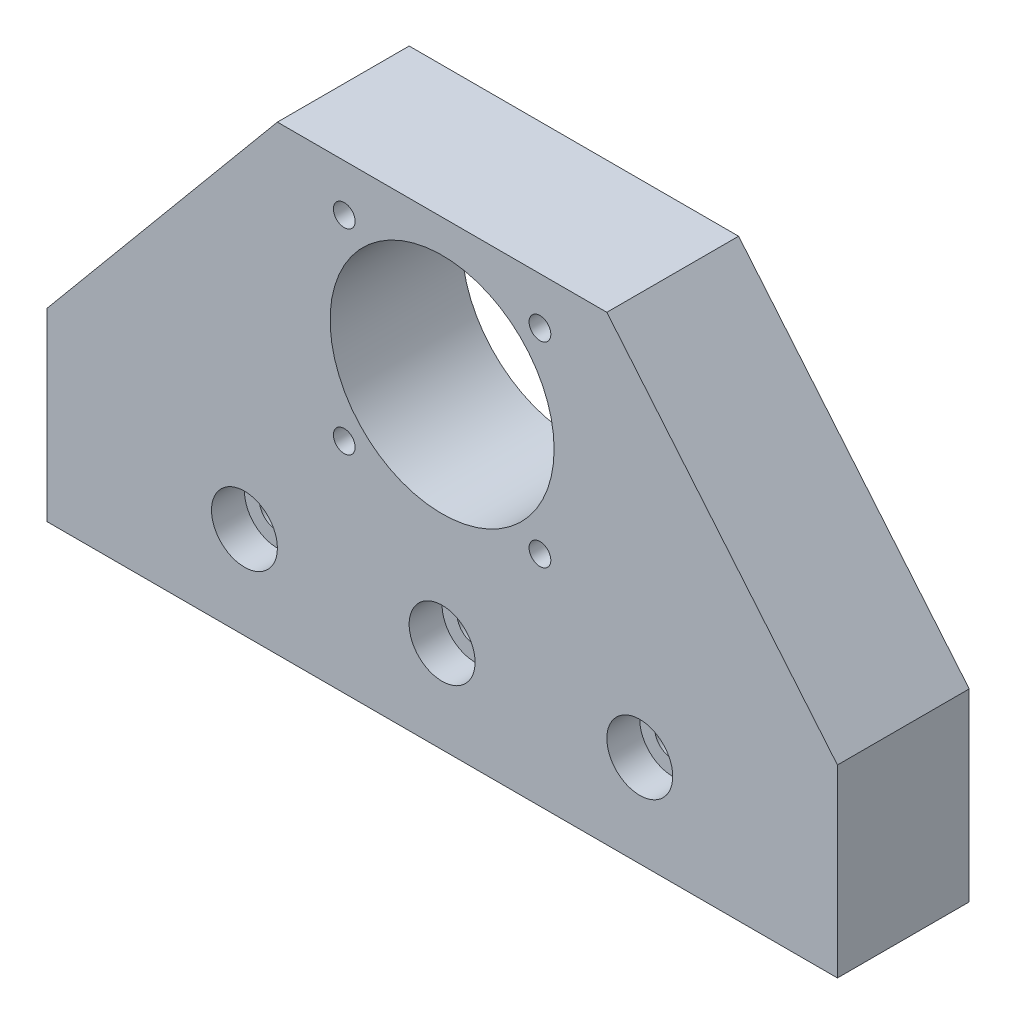
SolidWorks part; units mm, degrees
ref_plane "Front Plane" through (0, 0, 0) normal (0, 0, 1) x (1, 0, 0)
ref_plane "Top Plane" through (0, 0, 0) normal (0, 1, 0) x (1, 0, 0)
ref_plane "Right Plane" through (0, 0, 0) normal (1, 0, 0) x (0, 0, -1)
sketch "Sketch1" plane through (0, 0, 0) normal (0, 0, 1) x (1, 0, 0)
  line L0 (60, 0) -> (-60, 0)
  line L1 (-60, 0) -> (-60, 28)
  line L2 (-60, 28) -> (-25, 70)
  line L3 (-25, 70) -> (25, 70)
  line L4 (0, 0) -> (0, 70) construction
  line L5 (60, 28) -> (25, 70)
  line L6 (60, 0) -> (60, 28)
  dimension "D1" = 120
  dimension "D2" = 28
  dimension "D3" = 50
  dimension "D4" = 70
extrude "Boss-Extrude1" add sketch "Sketch1" along normal blind 20
sketch "Sketch2" plane through (0, 0, 20) normal (0, 0, 1) x (1, 0, 0)
  line L0 (0, 0) -> (0, 70) construction
  line L1 (-60, 0) -> (60, 0) construction
  line L2 (25, 70) -> (-25, 70) construction
  line L3 (-60, 14) -> (60, 14) construction
  line L4 (-60, 28) -> (-60, 0) construction
  line L5 (60, 0) -> (60, 28) construction
  point P12 (0, 14)
  point P13 (-30, 14)
  point P14 (30, 14)
  point P15 (0, 48)
  dimension "D1" = 30
hole_wizard "CBORE for M5 SHCS1" positions "3DSketch1" profile "Sketch3" counterbore size "M5" standard "ANSI Metric" end condition through all
sketch3d "3DSketch1"
  point P0 (-30, 14, 20)
  point P3 (0, 14, 20)
  point P6 (30, 14, 20)
sketch "Sketch3" plane through (-30, 14, 20) normal (1, 0, 0) x (0, -1, 0)
  line L0 (0, 0) -> (0, 20)
  line L1 (0, 20) -> (2.75, 20)
  line L3 (2.75, 20) -> (2.75, 5)
  line L4 (2.75, 5) -> (5, 5)
  line L5 (5, 5) -> (5, 0)
  line L7 (5, 0) -> (0, 0)
  line L11 (0, -6.35) -> (0, 107.95) construction
  dimension "Thru Hole Dia." = 5.5
  dimension "Thru Hole Depth" = 20
  dimension "C'Bore Dia." = 10
  dimension "C'Bore Depth" = 5
sketch "Sketch4" plane through (0, 0, 20) normal (0, 0, 1) x (1, 0, 0)
  circle A0 centre (0, 48) radius 17
  dimension "D1" = 34
extrude "Cut-Extrude1" cut sketch "Sketch4" against normal through all
sketch "Sketch5" plane through (0, 0, 20) normal (0, 0, 1) x (1, 0, 0)
  point P0 (14.8492, 33.1508)
  point P1 (-14.8492, 33.1508)
  point P2 (-14.8492, 62.8492)
  point P3 (14.8492, 62.8492)
hole_wizard "M4 Tapped Hole1" positions "3DSketch3" profile "Sketch7" tap size "M4" standard "ISO" end condition through all
sketch3d "3DSketch3"
  point P0 (-14.8492, 62.8492, 20)
  point P3 (14.8492, 62.8492, 20)
  point P6 (14.8492, 33.1508, 20)
  point P9 (-14.8492, 33.1508, 20)
sketch "Sketch7" plane through (-14.8492, 62.8492, 20) normal (1, 0, 0) x (0, -1, 0)
  line L0 (0, 0) -> (0, 20)
  line L1 (0, 20) -> (1.65, 20)
  line L2 (1.65, 20) -> (1.65, 0)
  line L5 (1.65, 0) -> (0, 0)
  line L11 (0, -6.35) -> (0, 107.95) construction
  dimension "Thread Major Dia." = 3.3
  dimension "Thru Tap Drill Depth" = 20
